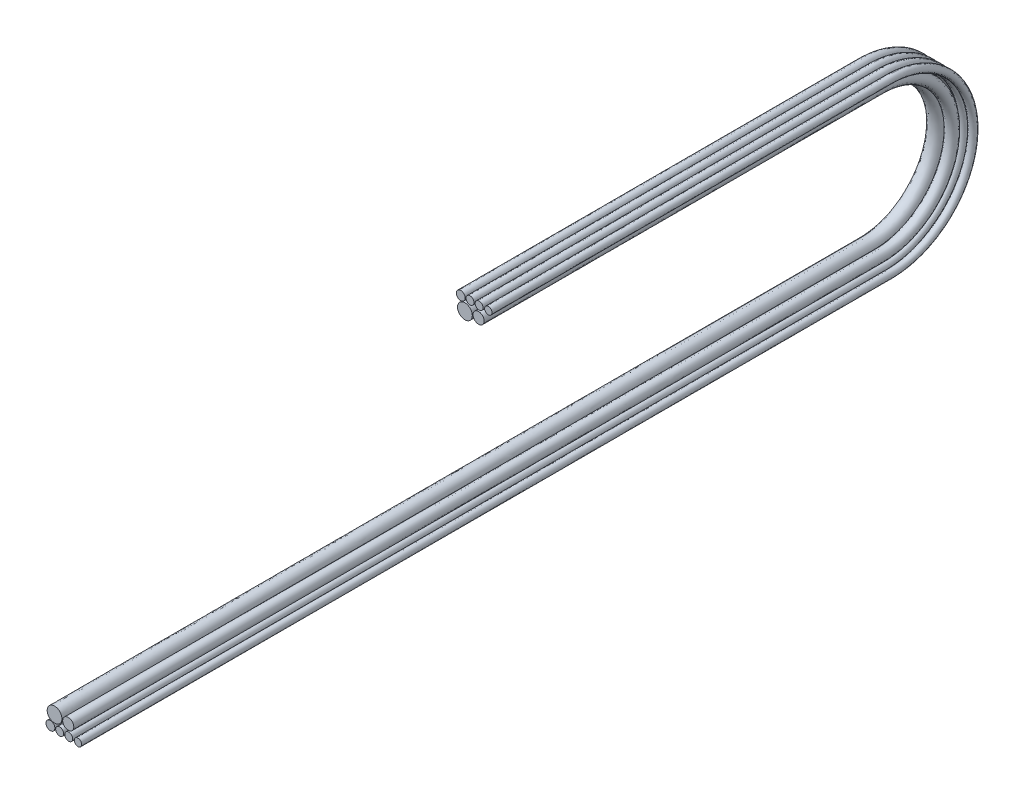
SolidWorks part; units mm, degrees
ref_plane "Front Plane" through (0, 0, 0) normal (0, 0, 1) x (1, 0, 0)
ref_plane "Top Plane" through (0, 0, 0) normal (0, 1, 0) x (1, 0, 0)
ref_plane "Right Plane" through (0, 0, 0) normal (1, 0, 0) x (0, 0, -1)
sketch "Sketch1" plane through (0, 0, 0) normal (0, 0, 1) x (1, 0, 0)
  line L1 (18.5, 18) -> (-18.5, 18) construction
  line L2 (18.5, 18) -> (18.5, 0) construction
  line L3 (18.5, 0) -> (-18.5, 0) construction
  line L4 (-18.5, 18) -> (-18.5, 0) construction
  circle A0 centre (-16.1, 2.4) radius 2.4
  circle A2 centre (-11.0983, 2.15) radius 2.15
  circle A5 centre (-6.1615, 2.15) radius 2.15
  circle A6 centre (-1.1864, 2) radius 2
  circle A7 centre (-13.8535, 8.6823) radius 4
  circle A8 centre (-6.4473, 8.0498) radius 3
  dimension "D3" = 4.8
  dimension "D4" = 4.3
  dimension "D6" = 4
  dimension "D7" = 8
  dimension "D8" = 6
  dimension "D1" = 37
  dimension "D2" = 18
sketch "Sketch2" plane through (0, 0, 0) normal (1, 0, 0) x (0, 0, -1)
  spline S1 degree 3 poles (-999.9965, 9.7) (-520.3574, 9.7) (-40.6464, 9.7) (439.1367, 9.7) (439.3527, 9.7023) (439.4967, 9.7043) (439.5686, 9.7055) (513.0411, 10.9584) (513.0411, 84.4416) (439.5686, 85.6945) (439.4967, 85.6957) (439.3527, 85.6977) (439.1367, 85.7) (33.4284, 85.7) (-372.2079, 85.7) (-777.7723, 85.7) knots -1.36443 -1.36443 -1.36443 -1.36443 0.598879 0.599173 0.599468 0.599763 0.599763 0.599763 0.703445 0.703445 0.703445 0.703739 0.704034 0.704329 2.364427 2.364427 2.364427 2.364427 weights 1 1 1 1 1 1 1 0.3447 0.3447 1 1 1 1 1 1 1 only from (0, 9.7) to (222.222, 85.7) construction
  spline S2 degree 3 poles (0, 9.7) (146.3069, 9.7) (292.6858, 9.7) (439.1367, 9.7) (439.3527, 9.7023) (439.4967, 9.7043) (439.5686, 9.7055) (513.0411, 10.9584) (513.0411, 84.4416) (439.5686, 85.6945) (439.4967, 85.6957) (439.3527, 85.6977) (439.1367, 85.7) (366.7598, 85.7) (294.4549, 85.7) (222.222, 85.7) knots 0 0 0 0 0.598879 0.599173 0.599468 0.599763 0.599763 0.599763 0.703445 0.703445 0.703445 0.703739 0.704034 0.704329 1 1 1 1 weights 1 1 1 1 1 1 1 0.3447 0.3447 1 1 1 1 1 1 1
sweep "Sweep1" add profiles "Sketch1" path "Sketch2"
